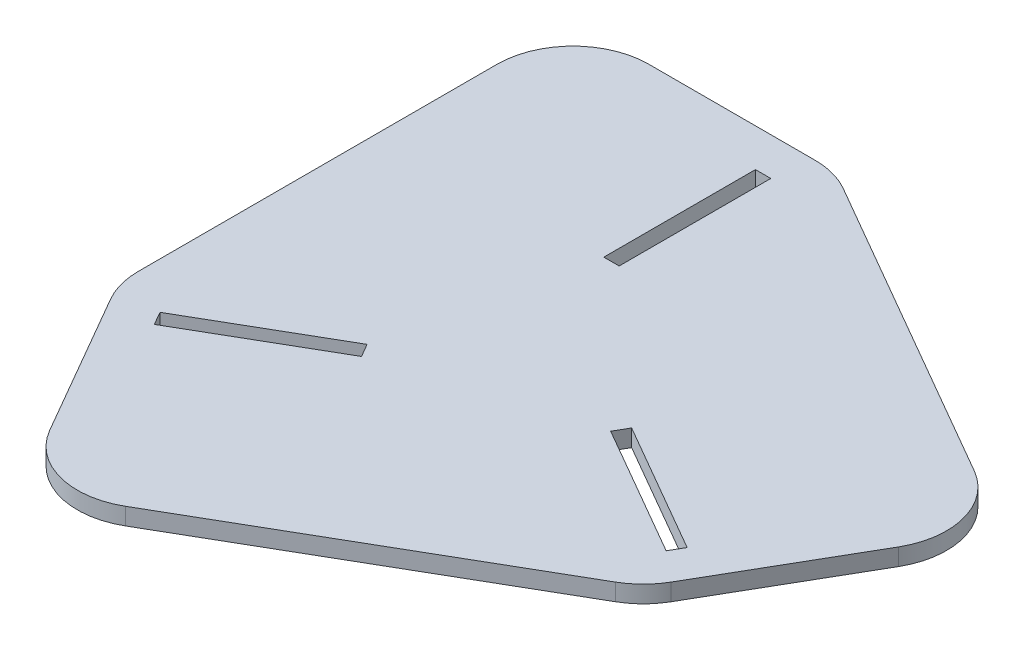
SolidWorks part; units mm, degrees
ref_plane "Front Plane" through (0, 0, 0) normal (0, 0, 1) x (1, 0, 0)
ref_plane "Top Plane" through (0, 0, 0) normal (0, 1, 0) x (1, 0, 0)
ref_plane "Right Plane" through (0, 0, 0) normal (1, 0, 0) x (0, 0, -1)
ref_axis "X Axis" through (-88.99, 0, 0) along (1, 0, 0)
ref_axis "Y Axiz" through (0, 0, 55) along (0, 0, -1)
ref_axis "Z Axis" through (0, 55, 0) along (0, -1, 0)
sketch "Sketch1" plane through (0, 0, 0) normal (0, 1, 0) x (1, 0, 0)
  line L0 (0, 0) -> (0, 164.1789) construction
  line L2 (0, 80) -> (-69.282, 80)
  line L3 (-58.141, 28.9) -> (-11.141, 28.9)
  line L4 (-58.141, 28.9) -> (-58.141, 71.1)
  line L5 (-58.141, 71.1) -> (-11.141, 71.1)
  line L6 (-11.141, 28.9) -> (-11.141, 71.1)
  line L7 (-69.282, 80) -> (-69.282, -40)
  line L9 (-58.141, 50) -> (-69.282, 50) construction
  line L10 (-11.141, 50) -> (0, 50) construction
  line L11 (0, 0) -> (69.282, -40)
  line L12 (69.282, -40) -> (103.923, 20)
  line L13 (54.0986, 35.9016) -> (30.5986, -4.8016)
  line L14 (54.0986, 35.9016) -> (90.6449, 14.8016)
  line L15 (90.6449, 14.8016) -> (67.1449, -25.9016)
  line L16 (30.5986, -4.8016) -> (67.1449, -25.9016)
  line L17 (103.923, 20) -> (0, 80)
  line L18 (0, 0) -> (142.1831, -82.0895) construction
  line L20 (72.3718, 25.3516) -> (77.9423, 35) construction
  line L21 (48.8718, -15.3516) -> (43.3013, -25) construction
  line L22 (0, 0) -> (-69.282, -40)
  line L23 (-69.282, -40) -> (-34.641, -100)
  line L24 (4.0424, -64.8016) -> (-19.4576, -24.0984)
  line L25 (4.0424, -64.8016) -> (-32.5039, -85.9016)
  line L26 (-32.5039, -85.9016) -> (-56.0039, -45.1984)
  line L27 (-19.4576, -24.0984) -> (-56.0039, -45.1984)
  line L28 (-34.641, -100) -> (69.282, -40)
  line L29 (0, 0) -> (-142.1831, -82.0895) construction
  line L31 (-14.2308, -75.3516) -> (-8.6603, -85) construction
  line L32 (-37.7308, -34.6484) -> (-43.3013, -25) construction
  line L33 (31.5513, -5.3516) -> (66.1923, -25.3516)
  line L34 (-11.141, 30) -> (-7.091, 30)
  line L35 (-11.141, 30) -> (-11.141, 70)
  line L36 (-11.141, 70) -> (-7.091, 70)
  line L37 (-7.091, 30) -> (-7.091, 70)
  line L38 (31.5513, -5.3516) -> (29.5263, -8.859)
  line L39 (29.5263, -8.859) -> (64.1673, -28.859)
  line L40 (66.1923, -25.3516) -> (64.1673, -28.859)
  line L41 (-20.4103, -24.6484) -> (-55.0513, -44.6484)
  line L42 (-20.4103, -24.6484) -> (-22.4353, -21.141)
  line L43 (-22.4353, -21.141) -> (-57.0763, -41.141)
  line L44 (-55.0513, -44.6484) -> (-57.0763, -41.141)
  line L45 (0, -2.475) -> (0, 2.475) construction
  circle A0 centre (0, 0) radius 105.8301 construction
  point P48 (0, 0)
  point P51 (-7.091, 50)
  point P62 (0, 0)
  dimension "D6" = 47
  dimension "D1" = 80
  dimension "D3" = 42.2
  dimension "D4" = 50
  dimension "D5" = 3
  dimension "D8" = 4.05
  dimension "D9" = 40
  dimension "D10" = 3
extrude "Boss-Extrude1" add sketch "Sketch1" along normal blind 4.5 contours L23 L28 L11 L22 L27 L44 L43 L42 L24 L25 L26 | L13 L16 L15 L14 | L3 L6 L5 L4 | L24 L27 L26 L25 | L22 L11 L12 L17 L2 L7 L37 L34 L6 L3 L4 L5 L36 L16 L40 L39 L38 L13 L14 L15 region at (-1.0252, 0, -21.8387) region at (2.0504, 0, 43.6774) region at (-34.641, 0, -50) region at (60.6218, 0, -5) region at (-25.9808, 0, 55)
fillet "Fillet1" radius 20 6 edges at (-69.282, 2.25, -80) (103.923, 2.25, -20) (-34.641, 2.25, 100) (69.282, 2.25, 40) (0, 2.25, -80) (-69.282, 2.25, 40)
